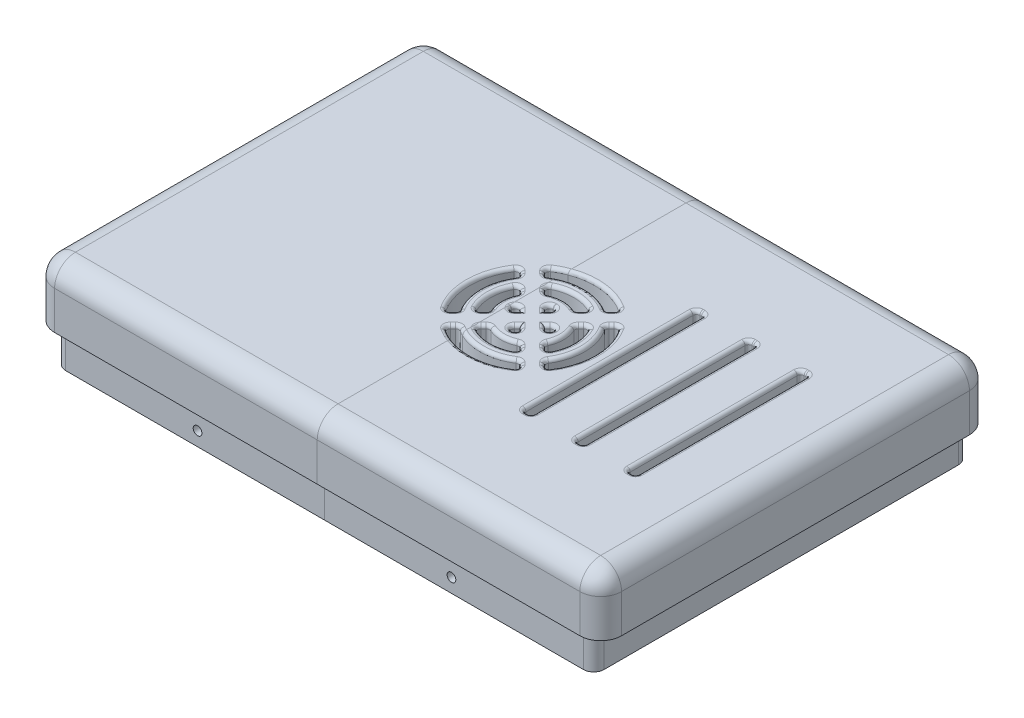
SolidWorks part; units mm, degrees
ref_plane "Plan de face" through (0, 0, 0) normal (0, 0, 1) x (1, 0, 0)
ref_plane "Plan de dessus" through (0, 0, 0) normal (0, 1, 0) x (1, 0, 0)
ref_plane "Plan de droite" through (0, 0, 0) normal (1, 0, 0) x (0, 0, -1)
sketch "Esquisse1" plane through (0, 0, 0) normal (0, 1, 0) x (1, 0, 0)
  line L1 (-81.5, 56) -> (81.5, 56)
  line L2 (-81.5, 56) -> (-81.5, -56)
  line L3 (-81.5, -56) -> (81.5, -56)
  line L4 (81.5, 56) -> (81.5, -56)
  line L5 (-81.5, 56) -> (81.5, -56) construction
  line L6 (-81.5, -56) -> (81.5, 56) construction
  point P0 (0, 0)
  dimension "D1" = 112
  dimension "D2" = 163
extrude "Boss.-Extru.1" add sketch "Esquisse1" along normal blind 7
sketch "Esquisse2" plane through (0, 0, 0) normal (0, -1, 0) x (1, 0, 0)
  line L1 (81.5, -56) -> (-81.5, -56)
  line L2 (81.5, -56) -> (81.5, 56)
  line L3 (81.5, 56) -> (-81.5, 56)
  line L4 (-81.5, -56) -> (-81.5, 56)
  line L5 (81.5, -56) -> (-81.5, 56) construction
  line L6 (81.5, 56) -> (-81.5, -56) construction
  line L7 (73.5, -51.5) -> (-73.5, -51.5)
  line L8 (73.5, -51.5) -> (73.5, 51.5)
  line L9 (73.5, 51.5) -> (-73.5, 51.5)
  line L10 (-73.5, -51.5) -> (-73.5, 51.5)
  line L11 (73.5, -51.5) -> (-73.5, 51.5) construction
  line L12 (73.5, 51.5) -> (-73.5, -51.5) construction
  point P0 (0, 0)
  point P7 (0, 0)
  dimension "D1" = 8
  dimension "D2" = 4.5
extrude "Boss.-Extru.2" add sketch "Esquisse2" along normal blind 20
sketch "Esquisse3" plane through (0, -20, 0) normal (0, -1, 0) x (-1, 0, 0)
  line L1 (-81.5, 56) -> (81.5, 56)
  line L2 (-81.5, 56) -> (-81.5, -56)
  line L3 (-81.5, -56) -> (81.5, -56)
  line L4 (81.5, 56) -> (81.5, -56)
  line L5 (-81.5, 56) -> (81.5, -56) construction
  line L6 (-81.5, -56) -> (81.5, 56) construction
  line L7 (-77.4, 53.9) -> (77.4, 53.9)
  line L8 (-77.4, 53.9) -> (-77.4, -53.9)
  line L9 (-77.4, -53.9) -> (77.4, -53.9)
  line L10 (77.4, 53.9) -> (77.4, -53.9)
  line L11 (-77.4, 53.9) -> (77.4, -53.9) construction
  line L12 (-77.4, -53.9) -> (77.4, 53.9) construction
  point P0 (0, 0)
  point P7 (0, 0)
  dimension "D1" = 2.1
  dimension "D2" = 4.1
extrude "Enlèv. mat.-Extru.1" cut sketch "Esquisse3" against normal blind 10
fillet "Congé1" radius 6 4 edges at (81.5, -1.5, 56) (81.5, -1.5, -56) (-81.5, -1.5, -56) (-81.5, -1.5, 56)
fillet "Congé2" radius 6 8 edges at (-79.7426, 7, 54.2426) (-81.5, 7, 0) (-79.7426, 7, -54.2426) (0, 7, -56) (79.7426, 7, -54.2426) (81.5, 7, 0) (79.7426, 7, 54.2426) (0, 7, 56)
fillet "Congé3" radius 3 4 edges at (73.5, 0, 0) (0, 0, -51.5) (-73.5, 0, 0) (0, 0, 51.5)
fillet "Congé4" radius 3 4 edges at (-77.4, -15, 53.9) (77.4, -15, 53.9) (77.4, -15, -53.9) (-77.4, -15, -53.9)
sketch "Esquisse4" plane through (0, 0, 0) normal (0, -1, 0) x (1, 0, 0)
  line L0 (6.5, 0.67) -> (-6.2279, 13.3979) construction
  line L1 (-73, -51) -> (73, -51)
  line L2 (-73, -51) -> (-73, 51)
  line L3 (-73, 51) -> (73, 51)
  line L4 (73, -51) -> (73, 51)
  line L5 (-73, -51) -> (73, 51) construction
  line L6 (-73, 51) -> (73, -51) construction
  line L7 (-2.5, 0.67) -> (-5.5, 0.67) construction
  line L8 (-5.5, 0.67) -> (-8.5, 0.67) construction
  line L9 (-8.5, 0.67) -> (-11.5, 0.67) construction
  line L10 (-2.5, 0.67) -> (0.5, 0.67) construction
  line L11 (0.5, 0.67) -> (3.5, 0.67) construction
  line L12 (3.5, 0.67) -> (6.5, 0.67) construction
  line L13 (6.5, 0.67) -> (19.2279, 13.3979) construction
  line L14 (6.5, 0.67) -> (19.2279, -12.0579) construction
  line L15 (6.5, 0.67) -> (-6.2279, -12.0579) construction
  line L16 (25.9454, -22.311) -> (-16.481, 20.1154)
  line L17 (25.9454, -22.311) -> (29.481, -18.7754)
  line L18 (-16.481, 20.1154) -> (-12.9454, 23.651)
  line L19 (29.481, -18.7754) -> (-12.9454, 23.651)
  line L20 (25.9454, -22.311) -> (-12.9454, 23.651) construction
  line L21 (-16.481, 20.1154) -> (29.481, -18.7754) construction
  line L22 (-12.9454, -22.311) -> (29.481, 20.1154)
  line L23 (-12.9454, -22.311) -> (-16.481, -18.7754)
  line L24 (29.481, 20.1154) -> (25.9454, 23.651)
  line L25 (-16.481, -18.7754) -> (25.9454, 23.651)
  line L26 (-12.9454, -22.311) -> (25.9454, 23.651) construction
  line L27 (29.481, 20.1154) -> (-16.481, -18.7754) construction
  circle A0 centre (6.5, 0.67) radius 18
  circle A1 centre (6.5, 0.67) radius 15
  circle A2 centre (6.5, 0.67) radius 12
  circle A3 centre (6.5, 0.67) radius 9
  circle A4 centre (6.5, 0.67) radius 6
  circle A5 centre (6.5, 0.67) radius 3
  point P0 (0, 0)
  point P6 (6.5, 0.67)
  dimension "D1" = 102
  dimension "D2" = 146
  dimension "D3" = 66.5
  dimension "D4" = 51.67
  dimension "D5" = 3
  dimension "D6" = 5
extrude "Enlèv. mat.-Extru.2" cut sketch "Esquisse4" against normal up to surface (7 mm away) contours L16 A4 L25 | A3 L16 A2 L25 | A1 L16 A0 L25 | A1 L22 A0 L16 | A3 L22 A2 L16 | L22 A4 L16 | A1 L19 A0 L22 | A3 L19 A2 L22 | L19 A4 L22 | L25 A4 L19 | A3 L25 A2 L19 | A1 L25 A0 L19 region at (6.5, 0, -14.7998) region at (21.9698, 0, 0.67) region at (6.5, 0, -9.4114) region at (-8.9698, 0, 0.67) region at (16.5814, 0, 0.67) region at (6.5, 0, -4.4228) region at (-3.5814, 0, 0.67) region at (6.5, 0, 16.1398) region at (11.5928, 0, 0.67) region at (1.4072, 0, 0.67) region at (6.5, 0, 10.7514) region at (6.5, 0, 5.7628) up to face at (0, 7, 0)
sketch "Esquisse5" plane through (0, 0, 0) normal (0, -1, 0) x (1, 0, 0)
  line L0 (6.5, 6.67) -> (6.5, -5.33) construction
  line L2 (22.55, -15.38) -> (-9.55, -15.38)
  line L3 (22.55, -15.38) -> (22.55, 16.72)
  line L4 (22.55, 16.72) -> (-9.55, 16.72)
  line L5 (-9.55, -15.38) -> (-9.55, 16.72)
  line L6 (22.55, -15.38) -> (-9.55, 16.72) construction
  line L7 (22.55, 16.72) -> (-9.55, -15.38) construction
  arc A0 (8.589, 6.2946) -> (4.411, 6.2946) centre (6.5, 0.67) ccw construction
  arc A1 (4.411, -4.9546) -> (8.589, -4.9546) centre (6.5, 0.67) ccw construction
  circle A3 centre (-9.55, 16.72) radius 1.25
  circle A4 centre (22.55, 16.72) radius 1.25
  circle A5 centre (22.55, -15.38) radius 1.25
  circle A6 centre (-9.55, -15.38) radius 1.25
  point P9 (6.5, 0.67)
  dimension "D3" = 2.5
  dimension "D1" = 32.1
  dimension "D2" = 32.1
extrude "Enlèv. mat.-Extru.3" cut sketch "Esquisse5" against normal blind 5 contours A3 | A6 | A4 | A5
fillet "Congé7" radius 1 128 edges at (19.7992, 7, -9.0936) (19.7992, 7, 10.4336) (19.7992, 0, 10.4336) (19.7992, 0, -9.0936) (15.4741, 7, -4.7685) (15.4741, 7, 6.1085) (15.4741, 0, 6.1085) (15.4741, 0, -4.7685) (-3.2636, 7, -12.6292) (16.2636, 7, -12.6292) (16.2636, 0, -12.6292) (-3.2636, 0, -12.6292) (1.0615, 7, -8.3041) (11.9385, 7, -8.3041) (11.9385, 0, -8.3041) (1.0615, 0, -8.3041) (11.0801, 7, -0.3745) (11.0801, 7, 1.7145) (11.0801, 0, 1.7145) (11.0801, 0, -0.3745) (5.4555, 7, -3.9101) (7.5445, 7, -3.9101) (7.5445, 0, -3.9101) (5.4555, 0, -3.9101) (-6.7992, 7, 10.4336) (-6.7992, 7, -9.0936) (-6.7992, 0, -9.0936) (-6.7992, 0, 10.4336) (-2.4741, 7, 6.1085) (-2.4741, 7, -4.7685) (-2.4741, 0, -4.7685) (-2.4741, 0, 6.1085) (1.9199, 7, 1.7145) (1.9199, 7, -0.3745) (1.9199, 0, -0.3745) (1.9199, 0, 1.7145) (7.5445, 7, 5.2501) (5.4555, 7, 5.2501) (5.4555, 0, 5.2501) (7.5445, 0, 5.2501) (11.9385, 7, 9.6441) (1.0615, 7, 9.6441) (1.0615, 0, 9.6441) (11.9385, 0, 9.6441) (16.2636, 7, 13.9692) (-3.2636, 7, 13.9692) (-3.2636, 0, 13.9692) (16.2636, 0, 13.9692) (14.3813, 3.5, -3.6757) (15.5, 0, 0.67) (14.3813, 3.5, 5.0157) (15.5, 7, 0.67) (18.726, 3.5, -8.0205) (21.5, 0, 0.67) (18.726, 3.5, 9.3605) (21.5, 7, 0.67) (2.1543, 3.5, -7.2113) (6.5, 0, -8.33) (10.8457, 3.5, -7.2113) (6.5, 7, -8.33) (-2.1905, 3.5, -11.556) (6.5, 0, -14.33) (15.1905, 3.5, -11.556) (6.5, 7, -14.33) (24.5, 7, 0.67) (20.8723, 3.5, 11.5068) (24.5, 0, 0.67) (20.8723, 3.5, -10.1668) (18.5, 7, 0.67) (16.5669, 3.5, 7.2013) (18.5, 0, 0.67) (16.5669, 3.5, -5.8613) (6.5, 7, -17.33) (17.3368, 3.5, -13.7023) (6.5, 0, -17.33) (-4.3368, 3.5, -13.7023) (6.5, 7, -11.33) (13.0313, 3.5, -9.3969) (6.5, 0, -11.33) (-0.0313, 3.5, -9.3969) (12.5, 7, 0.67) (12.1246, 3.5, 2.759) (12.5, 0, 0.67) (12.1246, 3.5, -1.419) (6.5, 7, -5.33) (8.589, 3.5, -4.9546) (6.5, 0, -5.33) (4.411, 3.5, -4.9546) (-5.726, 3.5, 9.3605) (-8.5, 0, 0.67) (-5.726, 3.5, -8.0205) (-8.5, 7, 0.67) (-1.3813, 3.5, 5.0157) (-2.5, 0, 0.67) (-1.3813, 3.5, -3.6757) (-2.5, 7, 0.67) (-11.5, 7, 0.67) (-7.8723, 3.5, -10.1668) (-11.5, 0, 0.67) (-7.8723, 3.5, 11.5068) (-5.5, 7, 0.67) (-3.5669, 3.5, -5.8613) (-5.5, 0, 0.67) (-3.5669, 3.5, 7.2013) (0.5, 7, 0.67) (0.8754, 3.5, -1.419) (0.5, 0, 0.67) (0.8754, 3.5, 2.759) (6.5, 7, 6.67) (4.411, 3.5, 6.2946) (6.5, 0, 6.67) (8.589, 3.5, 6.2946) (15.1905, 3.5, 12.896) (6.5, 0, 15.67) (-2.1905, 3.5, 12.896) (6.5, 7, 15.67) (10.8457, 3.5, 8.5513) (6.5, 0, 9.67) (2.1543, 3.5, 8.5513) (6.5, 7, 9.67) (6.5, 7, 12.67) (-0.0313, 3.5, 10.7369) (6.5, 0, 12.67) (13.0313, 3.5, 10.7369) (6.5, 7, 18.67) (-4.3368, 3.5, 15.0423) (6.5, 0, 18.67) (17.3368, 3.5, 15.0423)
sketch "Esquisse8" plane through (0, 7, 0) normal (0, 1, 0) x (1, 0, 0)
  line L0 (-75.5, 0) -> (75.5, 0) construction
  line L1 (-75.5, 50) -> (-75.5, -50) construction
  line L2 (75.5, -50) -> (75.5, 50) construction
  line L3 (43, -25) -> (45.5, -25)
  line L10 (58, -25) -> (60.5, -25)
  line L11 (58, -25) -> (58, 25)
  line L12 (58, 25) -> (60.5, 25)
  line L13 (60.5, -25) -> (60.5, 25)
  line L14 (58, -25) -> (60.5, 25) construction
  line L15 (58, 25) -> (60.5, -25) construction
  line L16 (43, -25) -> (43, 25)
  line L17 (45.5, -25) -> (45.5, 25)
  line L18 (43, 25) -> (45.5, 25)
  line L19 (28, -25) -> (30.5, -25)
  line L20 (28, -25) -> (28, 25)
  line L21 (30.5, -25) -> (30.5, 25)
  line L22 (28, 25) -> (30.5, 25)
  point P11 (59.25, 0)
  dimension "D4" = 50
  dimension "D5" = 2.5
  dimension "D6" = 15
  dimension "D7" = 3
extrude "Enlèv. mat.-Extru.4" cut sketch "Esquisse8" against normal up to surface (7 mm away) up to face at (11.3437, 0, 0.67)
fillet "Congé10" radius 1 36 edges at (29.25, 0, 25) (29.25, 7, 25) (59.25, 7, 25) (59.25, 0, 25) (58, 3.5, 25) (58, 7, 0) (58, 0, 0) (44.25, 7, 25) (44.25, 0, 25) (43, 3.5, 25) (43, 7, 0) (43, 0, 0) (60.5, 7, 0) (60.5, 3.5, 25) (60.5, 0, 0) (58, 3.5, -25) (59.25, 7, -25) (60.5, 3.5, -25) (59.25, 0, -25) (45.5, 7, 0) (45.5, 3.5, 25) (45.5, 0, 0) (43, 3.5, -25) (44.25, 7, -25) (45.5, 3.5, -25) (44.25, 0, -25) (30.5, 7, 0) (30.5, 3.5, 25) (30.5, 0, 0) (29.25, 7, -25) (30.5, 3.5, -25) (29.25, 0, -25) (28, 3.5, 25) (28, 7, 0) (28, 3.5, -25) (28, 0, 0)
ref_plane "Plan1" through (0, 0, 0) normal (1, 0, 0) x (0, 0, -1)
split "Fractionner1" trim tools "Plan1" bodies to split 109 resulting bodies 112 113
sketch "Esquisse9" plane through (0, 0, 53.9) normal (0, 0, 1) x (1, 0, 0)
  circle A0 centre (-36.5, -16) radius 1.25
  circle A1 centre (36.5, -16) radius 1.25
  dimension "D1" = 2.5
extrude "Enlèv. mat.-Extru.5" cut sketch "Esquisse9" against normal through all
